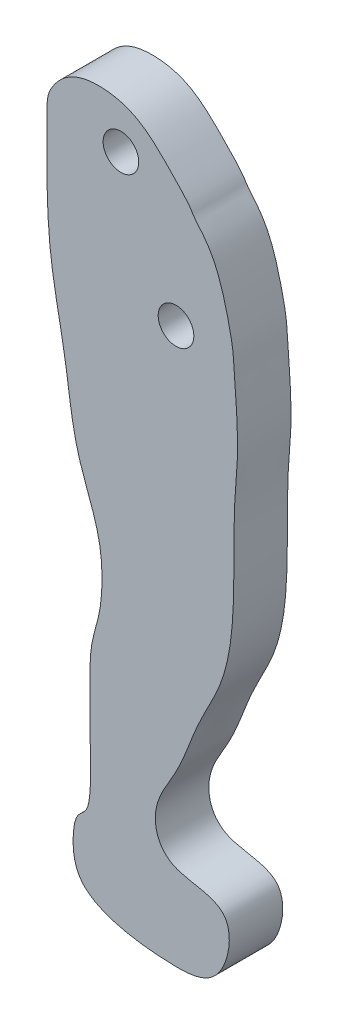
SolidWorks part; units mm, degrees
ref_plane "Спереди" through (0, 0, 0) normal (0, 0, 1) x (1, 0, 0)
ref_plane "Сверху" through (0, 0, 0) normal (0, 1, 0) x (1, 0, 0)
ref_plane "Справа" through (0, 0, 0) normal (1, 0, 0) x (0, 0, -1)
other "Configuration Table"
sketch "Sketch1" plane through (0, 0, 0) normal (0, 0, 1) x (1, 0, 0)
  circle A1 centre (-11.6768, 9.6204) radius 1
  circle A2 centre (-8.5867, 2.7149) radius 1
  spline S0 degree 3 poles (-15.8059, 9.7559) (-15.8432, 10.6624) (-14.2034, 12.3923) (-10.9765, 12.1549) (-7.2737, 8.5027) (-8.1671, 9.0798) (-6.2369, 7.0225) (-5.3362, 3.1296) (-5.3778, 2.6724) (-5.0192, -1.6642) (-5.4141, -4.2572) (-5.2486, -8.9874) (-5.6683, -13.0268) (-7.5009, -16.0957) (-8.3373, -18.8736) (-10.14, -21.2324) (-9.2846, -24.0832) (-5.0685, -23.8001) (-5.9522, -28.4141) (-8.6397, -28.4828) (-11.6439, -28.2121) (-14.3577, -27.2023) (-14.4332, -22.7996) (-13.3179, -24.4285) (-13.4762, -15.2767) (-13.433, -15.5242) (-12.7408, -12.8518) (-12.619, -9.6637) (-14.3124, -6.3542) (-14.7198, -1.9921) (-15.6924, 2.2501) (-15.8582, 5.8773) (-15.8059, 9.7559) (-15.8432, 10.6624) (-14.2034, 12.3923) knots -0.099933 -0.053487 -0.026157 0 0.01786 0.033406 0.045863 0.094555 0.11687 0.140451 0.165653 0.183319 0.216976 0.265684 0.311896 0.337994 0.370511 0.398546 0.422019 0.443802 0.463068 0.485048 0.499083 0.518507 0.536082 0.588519 0.607539 0.721495 0.738077 0.773363 0.817575 0.859523 0.900067 0.946513 0.973843 1 1.01786 1.033406 1.045863 only from (-15.4115, 11.0218) to (-15.4115, 11.0218)
  point P6 (-13.2689, -24.948)
  point P7 (-9.1728, 10.3666)
  point P8 (0, 0)
  point P9 (0, 0)
  point P10 (-6.7616, -25.7513)
  point P11 (0, 0)
  point P12 (-6.2255, -27.5678)
  point P14 (0, 0)
  point P16 (-9.1007, -28.4105)
  point P18 (-11.346, -28.1506)
  point P20 (-12.5329, -27.0368)
  point P22 (-13.398, -26.1116)
  point P24 (-12.8747, -27.6001)
  point P26 (-13.3905, -26.011)
  point P28 (-13.4141, -22.4366)
  point P30 (-13.392, -20.1015)
  point P32 (-13.8439, -26.0559)
  point P34 (-13.5041, -27.6307)
  point P36 (-14.4501, -25.4802)
  point P38 (-13.9223, -26.8656)
  point P40 (-14.3447, -24.8137)
  point P42 (0, 0)
  point P44 (-12.3409, -13.4138)
  point P46 (-12.8747, -13.302)
  point P48 (-11.6768, 9.6204)
  point P49 (-12.8685, -10.0527)
  point P52 (-8.6115, -23.622)
  point P54 (-5.8214, -24.686)
  point P56 (-8.5867, -1.1614)
  point P58 (-8.5867, 2.7149)
  point P60 (-5.0137, 6.9196)
  point P62 (0, 0)
  point P64 (-4.273, 5.6092)
  point P66 (-6.4096, 7.8597)
  point P68 (-3.4754, 3.7576)
  point P70 (-5.0992, 6.4069)
  point P71 (-13.7308, 12.1328)
  point P72 (-15.4115, 11.0218)
  point P73 (-4.6306, 3.603)
  point P74 (-6.3467, 6.6919)
  point P75 (-7.4106, 8.3051)
  point P76 (-4.356, 0.5826)
  point P77 (-4.356, -0.8589)
  point P78 (-5.2827, -4.0165)
  point P79 (-5.5083, 3.7641)
  point P80 (-5.3038, 1.8828)
  point P81 (-5.1466, -0.571)
  dimension "D2" = 2
extrude "Boss-Extrude1" add sketch "Sketch1" along normal blind 3
equation "\"R small\"= 2"
equation "\"R big\"= 4"
equation "\"width\"= 0.6"
equation "\"border width\"= 1"
equation "\"D2@Sketch1\"=\"R small\""
